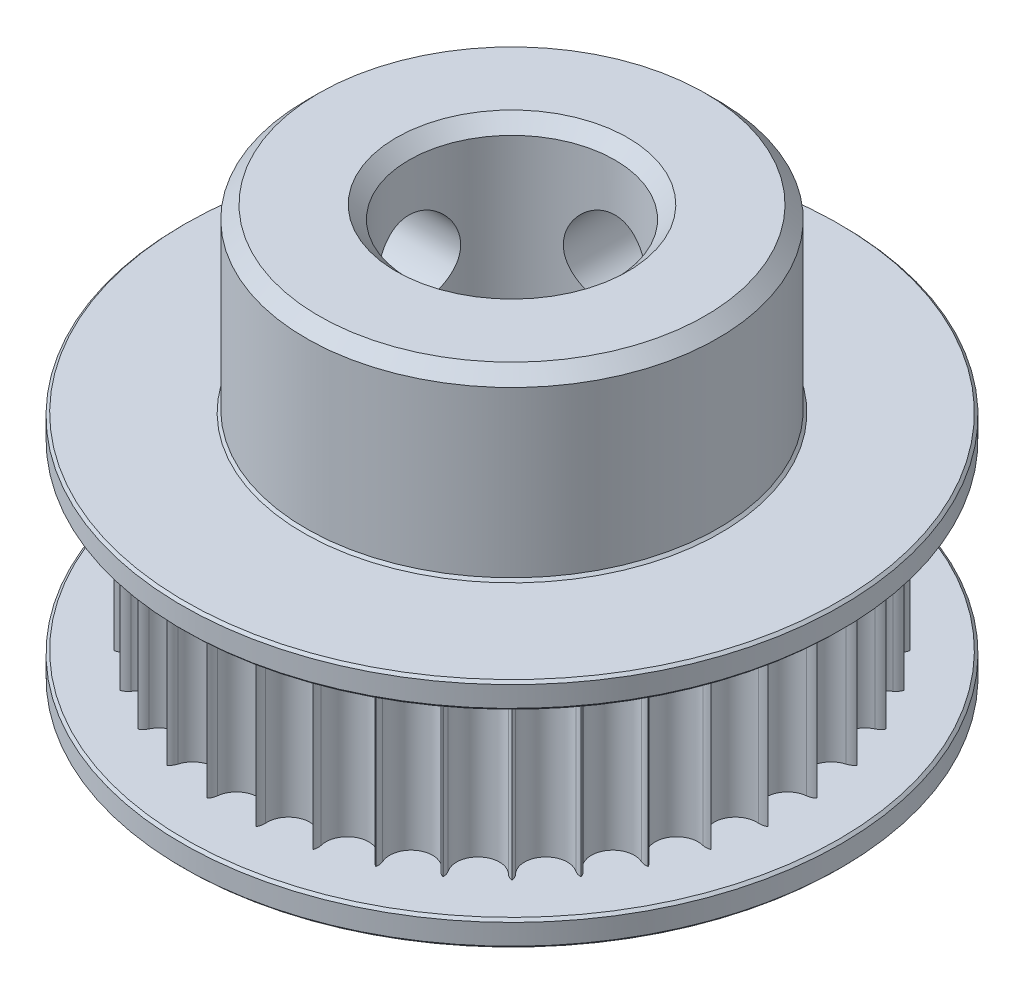
SolidWorks part; units mm, degrees
ref_plane "Front plan" through (0, 0, 0) normal (0, 0, 1) x (1, 0, 0)
ref_plane "Top plan" through (0, 0, 0) normal (0, 1, 0) x (1, 0, 0)
ref_plane "Right plan" through (0, 0, 0) normal (1, 0, 0) x (0, 0, -1)
sketch "Skica2" plane through (0, 0, 0) normal (0, 0, 1) x (1, 0, 0)
  line L0 (8, 8.5) -> (4, 8.5)
  line L1 (4, 8.5) -> (4, -8.5)
  line L2 (4, -8.5) -> (6.11, -8.5)
  line L3 (0, -8.5) -> (0, 8.5) construction
  line L4 (0, 8.5) -> (4, 8.5)
  line L5 (0, -8.5) -> (4, -8.5)
  line L6 (6.11, -8.5) -> (6.11, -7.5)
  line L7 (12.8, 0.5) -> (11.15, 0.5)
  line L8 (11.15, 0.5) -> (11.15, -6.5)
  line L9 (12.8, 0.5) -> (12.8, 1.5)
  line L12 (12.8, -7.5) -> (6.11, -7.5)
  line L13 (12.8, 1.5) -> (8, 1.5)
  line L14 (12.8, -7.5) -> (12.8, -6.5)
  line L15 (11.15, -6.5) -> (12.8, -6.5)
  line L16 (8, 1.5) -> (8, 8.5)
  point P6 (9.455, -7.5)
  point P7 (0, 0)
  dimension "D2" = 1
  dimension "D6" = 25.6
  dimension "D3" = 22.3
  dimension "D1" = 8
  dimension "D8" = 17
  dimension "D4" = 1
  dimension "D7" = 16
  dimension "D9" = 7
revolve "Revolute" add sketch "Skica2" angle 360 about L3 region at (7.218, -0.8166, 0)
sketch "Sketch2" plane through (0, 0.5, 0) normal (0, -1, 0) x (1, 0, 0)
  line L0 (0, 0) -> (0, 10.7023) construction
  line L1 (0, 0) -> (3.7597, 10.497) construction
  line L3 (0, 0) -> (-2.1589, 10.939) construction
  circle A1 centre (0, 0) radius 9.8663 construction
  circle A2 centre (0, 0) radius 10.65 construction
  arc A3 (-0.8317, 10.6175) -> (0.8317, 10.6175) centre (0, 10.7023) ccw
  arc A7 (-1.3915, 11.0628) -> (-2.1589, 10.939) centre (0, 0) ccw
  arc A8 (0, 12.5893) -> (2.1589, 10.939) centre (0.5977, 11.134) cw
  circle A9 centre (0, 0) radius 11.15 construction
  arc A10 (1.3915, 11.0628) -> (2.1589, 10.939) centre (0, 0) cw
  arc A11 (1.3915, 11.0628) -> (0.8317, 10.6175) centre (1.3291, 10.5667) ccw
  arc A12 (0, 12.5893) -> (-2.1589, 10.939) centre (-0.5977, 11.134) ccw
  arc A13 (-1.3915, 11.0628) -> (-0.8317, 10.6175) centre (-1.3291, 10.5667) cw
  point P0 (0, 0)
  circle M8 centre (0, 0) radius 11.15
  dimension "D2" = 1
  dimension "D4" = 0.836
  dimension "D6" = 22.3
  dimension "D3" = 1.5733
  dimension "D1" = 0.5
extrude "Cut-Extrude1" cut sketch "Sketch2" along normal up to surface (7 mm away) contours A8 M8 | A11 A3 M8 region at (0, 0.5, 10.6043) region at (0, 0.5, 11.8034) up to face at (12.8, -6.5, 0)
pattern_circular "CirPattern1" count 36 over 360 about axis through (0, -8.5, 0) along (0, -1, 0) of "Cut-Extrude1" reverse direction yes
sketch "Sketch3" plane through (0, 0, 0) normal (1, 0, 0) x (0, 0, -1)
  line L0 (0, 8.5) -> (0, 0.5) construction
  line L1 (4, 8.5) -> (-4, 8.5) construction
  circle A0 centre (0, 4.5) radius 1.65
  dimension "D1" = 3.3
extrude "Cut-Extrude2" cut sketch "Sketch3" against normal up to next
sketch "Sketch4" plane through (0, 0, 0) normal (0, 0, 1) x (1, 0, 0)
  line L0 (0, 8.5) -> (0, 0.5) construction
  line L1 (12.8, 8.5) -> (-12.8, 8.5) construction
  line L2 (-0.8317, 0.5) -> (0.8317, 0.5) construction
  circle A0 centre (0, 4.5) radius 1.65
  dimension "D1" = 3.3
extrude "Cut-Extrude3" cut sketch "Sketch4" against normal up to next
chamfer "Chamfer1" distance 1 angle 45 1 edges at (6.11, -7.5, 0)
chamfer "Chamfer2" distance 0.5 angle 45 2 edges at (8, 8.5, 0) (4, 8.5, 0)
chamfer "Chamfer3" distance 0.1 angle 45 5 edges at (12.8, -7.5, 0) (12.8, -6.5, 0) (12.8, 0.5, 0) (12.8, 1.5, 0) (8, 1.5, 0)
equation "\"`\"=2"
equation "\"D6@Sketch2\"= \"D3@Skica2\""
